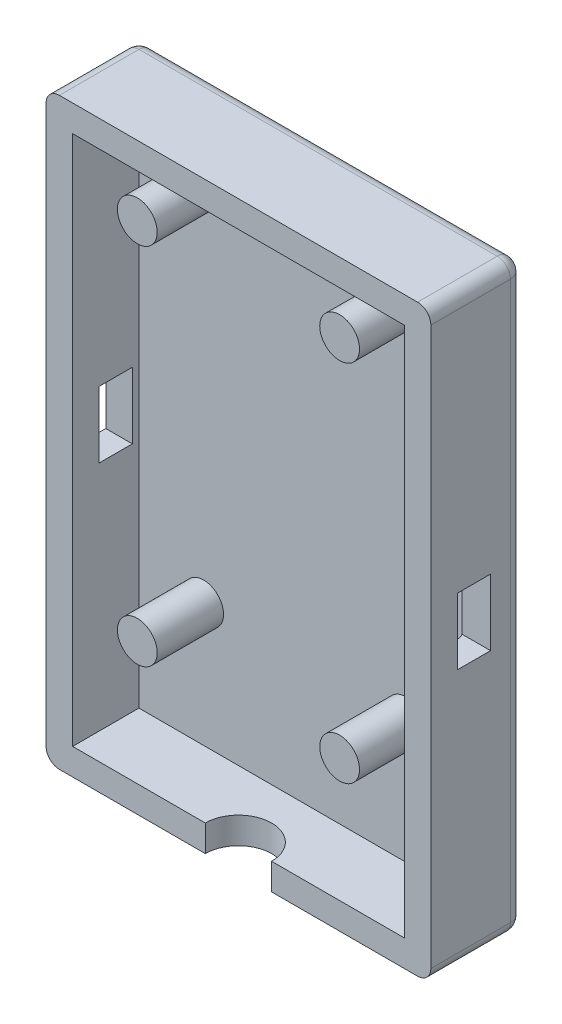
SolidWorks part; units mm, degrees
ref_plane "Front Plane" through (0, 0, 0) normal (0, 0, 1) x (1, 0, 0)
ref_plane "Top Plane" through (0, 0, 0) normal (0, 1, 0) x (1, 0, 0)
ref_plane "Right Plane" through (0, 0, 0) normal (1, 0, 0) x (0, 0, -1)
sketch "Sketch1" plane through (0, 0, 0) normal (0, 0, 1) x (1, 0, 0)
  line L1 (-14.5, 25.025) -> (14.5, 25.025)
  line L2 (-14.5, 25.025) -> (-14.5, -18.975)
  line L3 (-14.5, -18.975) -> (14.5, -18.975)
  line L4 (14.5, 25.025) -> (14.5, -18.975)
  point P0 (0, 0)
  point P6 (0, 0)
  dimension "D1" = 29
  dimension "D2" = 44
  dimension "D3" = 14.5
extrude "Boss-Extrude1" add sketch "Sketch1" along normal blind 2
sketch "Sketch2" plane through (0, 0, 2) normal (0, 0, 1) x (1, 0, 0)
  line L9 (12.5, 16.975) -> (12.5, -16.975)
  line L16 (-12.5, -16.975) -> (12.5, -16.975)
  line L18 (-14.5, 25.025) -> (14.5, 25.025)
  line L19 (-12.5, 16.975) -> (-12.5, -16.975)
  line L20 (14.5, -18.975) -> (14.5, 25.025) construction
  line L21 (14.5, 25.025) -> (14.5, -18.975)
  line L22 (14.5, -18.975) -> (-14.5, -18.975)
  line L23 (-14.5, -18.975) -> (14.5, -18.975) construction
  line L24 (-14.5, 25.025) -> (-14.5, -18.975) construction
  line L25 (-14.5, -18.975) -> (-14.5, 25.025)
  line L26 (-12.5, 16.975) -> (-12.5, 23.025)
  line L27 (-12.5, 23.025) -> (12.5, 23.025)
  line L28 (12.5, 23.025) -> (12.5, 16.975)
  dimension "D1" = 2
  dimension "D2" = 2
  dimension "D3" = 2
  dimension "D4" = 2
extrude "Boss-Extrude2" add sketch "Sketch2" along normal blind 5
sketch "Sketch4" plane through (0, -16.975, 0) normal (0, 1, 0) x (1, 0, 0)
  line L0 (-12.5, -7) -> (12.5, -7) construction
  line L2 (-2.5, -7) -> (2.5, -7)
  arc A1 (2.5, -7) -> (-2.5, -7) centre (0, -7) ccw
  dimension "D1" = 5
extrude "Cut-Extrude1" cut sketch "Sketch4" against normal through all
sketch "Sketch5" plane through (-14.5, 0, 0) normal (-1, 0, 0) x (0, 0, 1)
  line L0 (5, 5.525) -> (5, 0.525)
  line L1 (4.5, 5.525) -> (5, 5.525)
  line L5 (4.5, 5.525) -> (2.5, 5.525)
  line L9 (4.5, 0.525) -> (2.5, 0.525)
  line L11 (5, 0.525) -> (4.5, 0.525)
  line L13 (2.5, 5.525) -> (2.5, 0.525)
  dimension "D1" = 0.5
extrude "Cut-Extrude2" cut sketch "Sketch5" against normal through all
sketch "Sketch8" plane through (0, 0, 2) normal (0, 0, 1) x (1, 0, 0)
  circle A0 centre (-7.625, 19.775) radius 1.5
  circle A1 centre (-7.625, -7.675) radius 1.5
  circle A2 centre (7.625, -7.675) radius 1.5
  circle A3 centre (7.625, 19.775) radius 1.5
  dimension "D6" = 3
extrude "Boss-Extrude3" add sketch "Sketch8" along normal blind 5
fillet "Fillet1" radius 1 9 edges at (14.5, 3.025, 0) (0, -18.975, 0) (14.5, -18.975, 3.5) (-14.5, -18.975, 3.5) (-14.5, 25.025, 3.5) (14.5, 25.025, 3.5) (12.5, 3.025, 2) (0, 25.025, 0) (-14.5, 3.025, 0)
